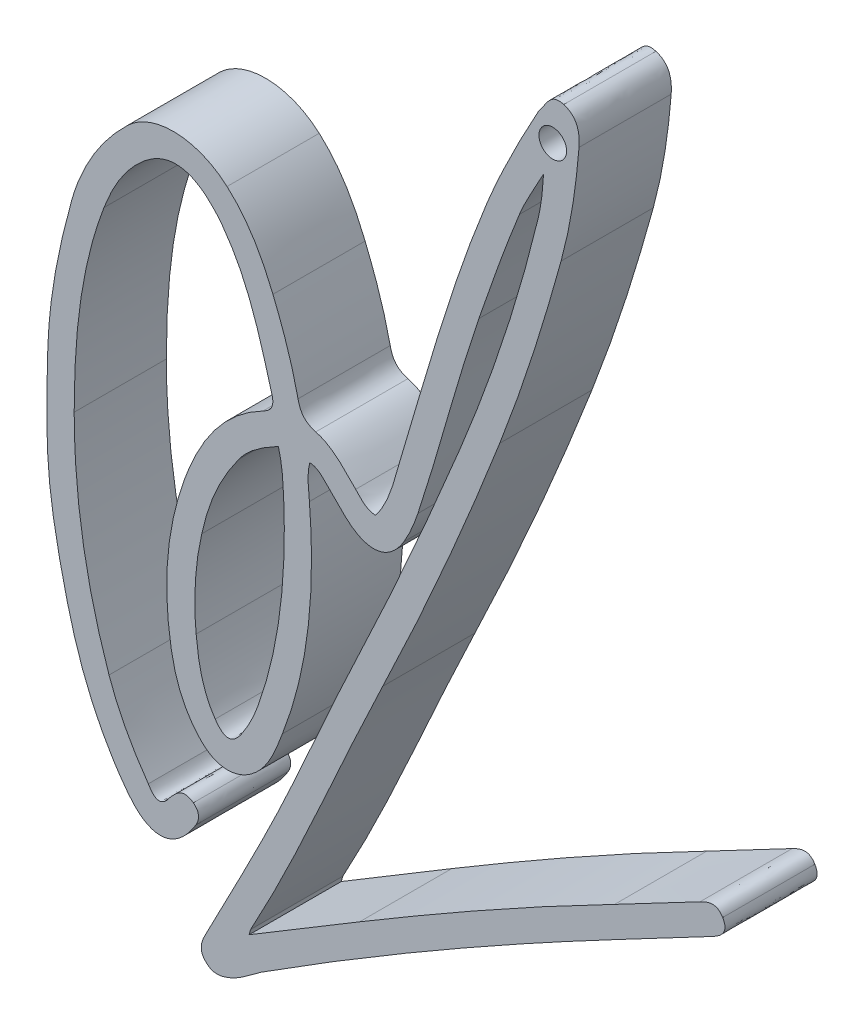
SolidWorks part; units mm, degrees
ref_plane "Płaszczyzna przednia" through (0, 0, 0) normal (0, 0, 1) x (1, 0, 0)
ref_plane "Płaszczyzna górna" through (0, 0, 0) normal (0, 1, 0) x (1, 0, 0)
ref_plane "Płaszczyzna prawa" through (0, 0, 0) normal (1, 0, 0) x (0, 0, -1)
sketch "Model" plane through (0, 0, 0) normal (0, 0, 1) x (1, 0, 0)
  spline S0 degree 3 poles (23.8841, 20.0035) (24.1817, 19.4835) (24.4731, 19.4698) (24.7966, 19.9211) knots 0 0 0 0 1 1 1 1
  spline S1 degree 3 poles (24.7966, 19.9211) (24.8687, 20.0219) (24.9648, 20.1058) (25.052, 20.1954) knots 0 0 0 0 1 1 1 1
  spline S2 degree 3 poles (25.052, 20.1954) (25.2938, 20.444) (25.5718, 20.4679) (25.8373, 20.2635) knots 0 0 0 0 1 1 1 1
  spline S3 degree 3 poles (25.8373, 20.2635) (26.1103, 20.0532) (26.1229, 19.7724) (25.9466, 19.4843) knots 0 0 0 0 1 1 1 1
  spline S4 degree 3 poles (25.9466, 19.4843) (25.1013, 18.1028) (24.0147, 17.8779) (22.995, 19.2265) knots 0 0 0 0 1 1 1 1
  spline S5 degree 3 poles (22.995, 19.2265) (21.6669, 20.9829) (20.8755, 22.9857) (20.3627, 25.1085) knots 0 0 0 0 1 1 1 1
  spline S6 degree 3 poles (20.3627, 25.1085) (19.9535, 26.8027) (19.594, 28.5174) (19.5155, 30.2538) knots 0 0 0 0 1 1 1 1
  spline S7 degree 3 poles (19.5155, 30.2538) (19.4559, 31.573) (19.4776, 32.9046) (19.5239, 34.2336) knots 0 0 0 0 1 1 1 1
  spline S8 degree 3 poles (19.5239, 34.2336) (19.5955, 36.2843) (20.0065, 38.2556) (20.5457, 40.2145) knots 0 0 0 0 1 1 1 1
  spline S9 degree 3 poles (20.5457, 40.2145) (20.9812, 41.7965) (21.7959, 43.152) (22.9821, 44.2907) knots 0 0 0 0 1 1 1 1
  spline S10 degree 3 poles (22.9821, 44.2907) (24.1107, 45.3742) (26.0119, 45.3028) (27.3002, 44.1534) knots 0 0 0 0 1 1 1 1
  spline S11 degree 3 poles (27.3002, 44.1534) (28.246, 43.3096) (28.8255, 42.238) (29.2909, 41.0994) knots 0 0 0 0 1 1 1 1
  spline S12 degree 3 poles (29.2909, 41.0994) (29.7393, 40.0026) (30.1306, 38.8808) (30.3805, 37.7174) knots 0 0 0 0 1 1 1 1
  spline S13 degree 3 poles (30.3805, 37.7174) (30.4743, 37.2804) (30.6607, 36.9908) (31.1498, 36.8581) knots 0 0 0 0 1 1 1 1
  spline S14 degree 3 poles (31.1498, 36.8581) (31.8762, 36.6609) (32.3706, 36.0895) (32.8813, 35.5664) knots 0 0 0 0 1 1 1 1
  spline S15 degree 3 poles (32.8813, 35.5664) (33.1106, 35.3315) (33.3135, 35.0488) (33.7394, 35.0198) knots 0 0 0 0 1 1 1 1
  spline S16 degree 3 poles (33.7394, 35.0198) (34.381, 35.8235) (34.5769, 36.8397) (34.865, 37.8044) knots 0 0 0 0 1 1 1 1
  spline S17 degree 3 poles (34.865, 37.8044) (36.0072, 41.6294) (37.0646, 45.4817) (38.5839, 49.1828) knots 0 0 0 0 1 1 1 1
  spline S18 degree 3 poles (38.5839, 49.1828) (39.2245, 50.7435) (39.9903, 52.2448) (40.8058, 53.7208) knots 0 0 0 0 1 1 1 1
  spline S19 degree 3 poles (40.8058, 53.7208) (40.8258, 53.7571) (40.8516, 53.7907) (40.8777, 53.8231) knots 0 0 0 0 1 1 1 1
  spline S20 degree 3 poles (40.8777, 53.8231) (41.1534, 54.1648) (41.3327, 54.7126) (41.9095, 54.5394) knots 0 0 0 0 1 1 1 1
  spline S21 degree 3 poles (41.9095, 54.5394) (42.5171, 54.357) (42.6145, 53.7877) (42.5717, 53.26) knots 0 0 0 0 1 1 1 1
  spline S22 degree 3 poles (42.5717, 53.26) (42.444, 51.6866) (42.2139, 50.1238) (41.7939, 48.5995) knots 0 0 0 0 1 1 1 1
  spline S23 degree 3 poles (41.7939, 48.5995) (41.0317, 45.8338) (40.1729, 43.1008) (39.1327, 40.4223) knots 0 0 0 0 1 1 1 1
  spline S24 degree 3 poles (39.1327, 40.4223) (37.5948, 36.4623) (35.9033, 32.5686) (34.0536, 28.7489) knots 0 0 0 0 1 1 1 1
  spline S25 degree 3 poles (34.0536, 28.7489) (32.1217, 24.7594) (30.4602, 20.641) (28.3243, 16.7496) knots 0 0 0 0 1 1 1 1
  spline S26 degree 3 poles (28.3243, 16.7496) (28.2972, 16.7001) (28.2919, 16.6388) (28.2581, 16.5168) knots 0 0 0 0 1 1 1 1
  spline S27 degree 3 poles (28.2581, 16.5168) (29.8888, 17.4977) (31.4676, 18.4524) (33.0512, 19.399) knots 0 0 0 0 1 1 1 1
  spline S28 degree 3 poles (33.0512, 19.399) (36.6797, 21.568) (40.355, 23.6532) (44.1156, 25.5865) knots 0 0 0 0 1 1 1 1
  spline S29 degree 3 poles (44.1156, 25.5865) (45.3563, 26.2244) (46.5854, 26.8848) (47.8196, 27.5353) knots 0 0 0 0 1 1 1 1
  spline S30 degree 3 poles (47.8196, 27.5353) (48.1724, 27.7213) (48.5618, 27.8588) (48.8063, 27.4381) knots 0 0 0 0 1 1 1 1
  spline S31 degree 3 poles (48.8063, 27.4381) (49.0697, 26.9849) (48.7646, 26.7167) (48.3716, 26.5083) knots 0 0 0 0 1 1 1 1
  spline S32 degree 3 poles (48.3716, 26.5083) (45.6151, 25.0465) (42.843, 23.6126) (40.1132, 22.1024) knots 0 0 0 0 1 1 1 1
  spline S33 degree 3 poles (40.1132, 22.1024) (36.2731, 19.978) (32.4911, 17.7521) (28.7969, 15.38) knots 0 0 0 0 1 1 1 1
  spline S34 degree 3 poles (28.7969, 15.38) (28.3254, 15.0773) (27.9216, 14.6721) (27.386, 14.4658) knots 0 0 0 0 1 1 1 1
  spline S35 degree 3 poles (27.386, 14.4658) (27.04, 14.3325) (26.6968, 14.2481) (26.3972, 14.5394) knots 0 0 0 0 1 1 1 1
  spline S36 degree 3 poles (26.3972, 14.5394) (26.0733, 14.8543) (26.158, 15.1782) (26.3527, 15.553) knots 0 0 0 0 1 1 1 1
  spline S37 degree 3 poles (26.3527, 15.553) (27.4267, 17.6215) (28.5172, 19.6833) (29.5226, 21.7854) knots 0 0 0 0 1 1 1 1
  spline S38 degree 3 poles (29.5226, 21.7854) (30.6529, 24.1486) (31.66, 26.5707) (32.7906, 28.9338) knots 0 0 0 0 1 1 1 1
  spline S39 degree 3 poles (32.7906, 28.9338) (34.4261, 32.3518) (35.9555, 35.8147) (37.3982, 39.3175) knots 0 0 0 0 1 1 1 1
  spline S40 degree 3 poles (37.3982, 39.3175) (38.7862, 42.6876) (39.9382, 46.1344) (40.7925, 49.6781) knots 0 0 0 0 1 1 1 1
  spline S41 degree 3 poles (40.7925, 49.6781) (40.9328, 50.26) (41.0005, 50.8595) (41.033, 51.488) knots 0 0 0 0 1 1 1 1
  spline S42 degree 3 poles (41.033, 51.488) (40.6808, 50.8109) (40.2727, 50.1565) (39.9879, 49.4522) knots 0 0 0 0 1 1 1 1
  spline S43 degree 3 poles (39.9879, 49.4522) (39.3493, 47.8727) (38.7769, 46.2687) (38.2254, 44.6538) knots 0 0 0 0 1 1 1 1
  spline S44 degree 3 poles (38.2254, 44.6538) (37.2502, 41.7981) (36.5266, 38.87) (35.5805, 36.0087) knots 0 0 0 0 1 1 1 1
  spline S45 degree 3 poles (35.5805, 36.0087) (35.4246, 35.5371) (35.2281, 35.0667) (34.9725, 34.6427) knots 0 0 0 0 1 1 1 1
  spline S46 degree 3 poles (34.9725, 34.6427) (34.3096, 33.543) (33.3767, 33.4314) (32.4387, 34.3072) knots 0 0 0 0 1 1 1 1
  spline S47 degree 3 poles (32.4387, 34.3072) (32.1342, 34.5916) (31.8476, 34.8953) (31.5539, 35.1913) knots 0 0 0 0 1 1 1 1
  spline S48 degree 3 poles (31.5539, 35.1913) (31.3786, 35.368) (31.2052, 35.5464) (30.8908, 35.5766) knots 0 0 0 0 1 1 1 1
  spline S49 degree 3 poles (30.8908, 35.5766) (30.7609, 35.0763) (30.8353, 34.5754) (30.8739, 34.1021) knots 0 0 0 0 1 1 1 1
  spline S50 degree 3 poles (30.8739, 34.1021) (31.1336, 30.9103) (30.8653, 27.7876) (29.6996, 24.7847) knots 0 0 0 0 1 1 1 1
  spline S51 degree 3 poles (29.6996, 24.7847) (29.3883, 23.9827) (29.0893, 23.1415) (28.3382, 22.5951) knots 0 0 0 0 1 1 1 1
  spline S52 degree 3 poles (28.3382, 22.5951) (27.6264, 22.0772) (26.8145, 22.1224) (26.1889, 22.7513) knots 0 0 0 0 1 1 1 1
  spline S53 degree 3 poles (26.1889, 22.7513) (25.4232, 23.5212) (25.061, 24.5105) (24.8837, 25.5382) knots 0 0 0 0 1 1 1 1
  spline S54 degree 3 poles (24.8837, 25.5382) (24.4891, 27.8252) (24.6673, 30.0824) (25.4705, 32.2729) knots 0 0 0 0 1 1 1 1
  spline S55 degree 3 poles (25.4705, 32.2729) (26.1252, 34.0585) (27.1055, 35.5923) (28.8567, 36.4971) knots 0 0 0 0 1 1 1 1
  spline S56 degree 3 poles (28.8567, 36.4971) (29.2233, 36.6865) (29.3653, 36.905) (29.2443, 37.3314) knots 0 0 0 0 1 1 1 1
  spline S57 degree 3 poles (29.2443, 37.3314) (28.7221, 39.1715) (28.2592, 41.0341) (27.0865, 42.6049) knots 0 0 0 0 1 1 1 1
  spline S58 degree 3 poles (27.0865, 42.6049) (26.8886, 42.8699) (26.6547, 43.1163) (26.4035, 43.3317) knots 0 0 0 0 1 1 1 1
  spline S59 degree 3 poles (26.4035, 43.3317) (25.5438, 44.0691) (24.632, 44.0679) (23.7491, 43.3544) knots 0 0 0 0 1 1 1 1
  spline S60 degree 3 poles (23.7491, 43.3544) (22.8779, 42.6504) (22.3404, 41.7004) (21.9576, 40.6895) knots 0 0 0 0 1 1 1 1
  spline S61 degree 3 poles (21.9576, 40.6895) (20.9426, 38.0088) (20.6647, 35.2139) (20.6674, 32.3562) knots 0 0 0 0 1 1 1 1
  spline S62 degree 3 poles (20.6674, 32.3562) (20.6704, 29.2211) (21.1538, 26.1882) (22.1792, 23.2371) knots 0 0 0 0 1 1 1 1
  spline S63 degree 3 poles (22.1792, 23.2371) (22.5772, 22.0915) (23.1512, 21.0279) (23.8841, 20.0035) knots 0 0 0 0 1 1 1 1
  spline S64 degree 3 poles (26.2033, 30.5564) (25.9041, 29.2735) (25.8369, 27.9695) (25.9598, 26.6667) knots 0 0 0 0 1 1 1 1
  spline S65 degree 3 poles (25.9598, 26.6667) (26.0513, 25.6959) (26.2087, 24.7174) (26.785, 23.8851) knots 0 0 0 0 1 1 1 1
  spline S66 degree 3 poles (26.785, 23.8851) (27.1885, 23.3024) (27.5385, 23.3213) (27.9357, 23.9053) knots 0 0 0 0 1 1 1 1
  spline S67 degree 3 poles (27.9357, 23.9053) (28.23, 24.338) (28.4607, 24.8005) (28.6374, 25.2941) knots 0 0 0 0 1 1 1 1
  spline S68 degree 3 poles (28.6374, 25.2941) (29.6134, 28.0202) (29.8809, 30.8382) (29.7566, 33.7108) knots 0 0 0 0 1 1 1 1
  spline S69 degree 3 poles (29.7566, 33.7108) (29.7316, 34.2889) (29.6984, 34.8616) (29.528, 35.5011) knots 0 0 0 0 1 1 1 1
  spline S70 degree 3 poles (29.528, 35.5011) (28.8429, 35.1341) (28.2467, 34.7559) (27.8067, 34.1542) knots 0 0 0 0 1 1 1 1
  spline S71 degree 3 poles (27.8067, 34.1542) (27.0347, 33.0985) (26.4954, 31.9409) (26.2033, 30.5564) knots 0 0 0 0 1 1 1 1
  point P72 (0, 0)
  point P73 (0, 0)
  dimension "D1" = 40
extrude "Dodanie-wyciągnięcie1" add sketch "Model" along normal blind 4
sketch "Szkic2" plane through (0, 0, 4) normal (0, 0, 1) x (1, 0, 0)
  line L0 (40.3317, 52.8481) -> (42.5358, 52.8481) construction
  line L1 (41.9095, 54.5394) -> (41.033, 51.488) construction
  circle A0 centre (41.4338, 52.8481) radius 0.6
  spline S3 degree 3 poles (40.8058, 53.7208) (39.9903, 52.2448) (39.2245, 50.7435) (38.5839, 49.1828) knots 0 0 0 0 1 1 1 1 construction
  spline S4 degree 3 poles (41.7939, 48.5995) (42.2139, 50.1238) (42.444, 51.6866) (42.5717, 53.26) knots 0 0 0 0 1 1 1 1 construction
  point P13 (0, 0)
  dimension "D1" = 1.2
  dimension "D2" = 1.1021
  dimension "D3" = 1.1021
extrude "Wytnij-wyciągnięcie1" cut sketch "Szkic2" against normal blind 5
